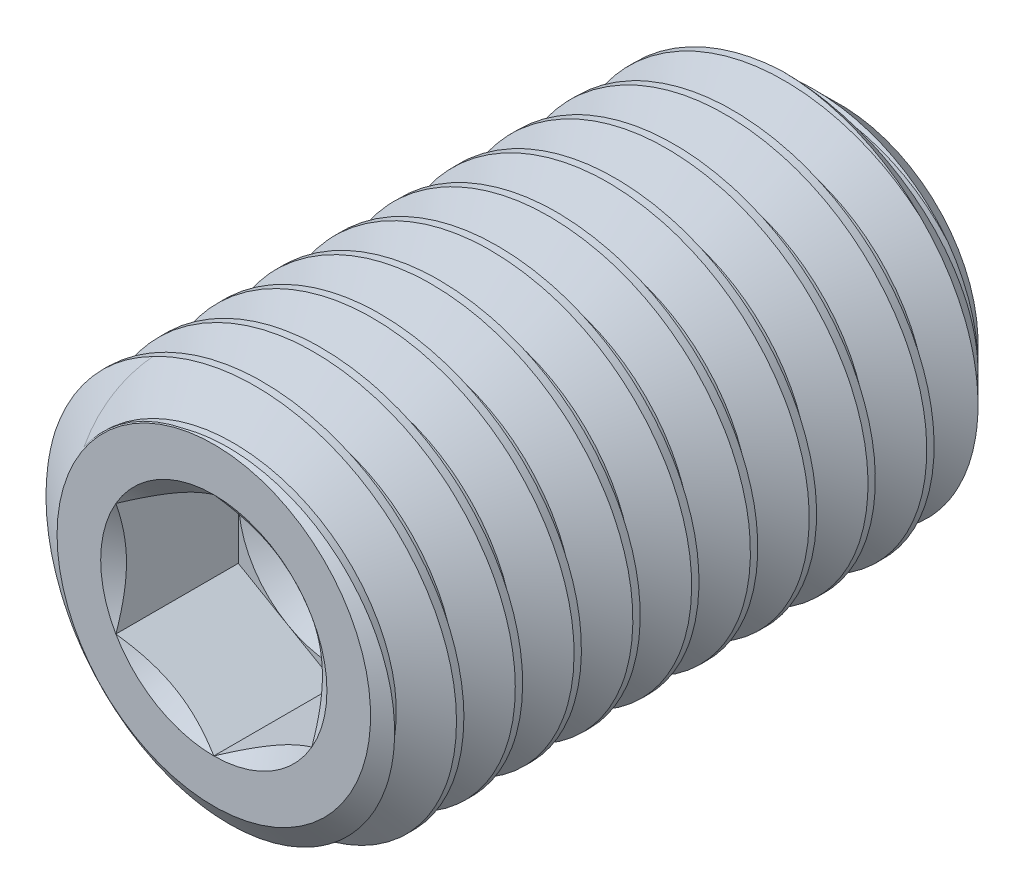
SolidWorks part; units mm, degrees
ref_plane "Front" through (0, 0, 0) normal (0, 0, 1) x (1, 0, 0)
ref_plane "Top" through (0, 0, 0) normal (0, 1, 0) x (1, 0, 0)
ref_plane "Right" through (0, 0, 0) normal (1, 0, 0) x (0, 0, -1)
sketch "Sketch22" plane through (0, 0, 0) normal (1, 0, 0) x (0, 0, -1)
  line L0 (-8, 0) -> (-8, 4)
  line L1 (-8, 4) -> (-7.2998, 5)
  line L2 (-7.2998, 5) -> (6.5, 5)
  line L3 (6.5, 5) -> (8, 3.5)
  line L4 (-0.3999, 5) -> (-0.3999, -5) construction
  line L5 (8, 0) -> (-8, 0)
  line L6 (-8, 4) -> (-8, -4) construction
  line L7 (8, 0) -> (8, 3.5)
  point P11 (-0.3999, 0)
  dimension "Length" = 16
  dimension "D3" = 35
  dimension "D6" = 45
  dimension "Dia" = 10
  dimension "D1" = 8
  dimension "D2" = 1.5
revolve "Revolve1" add sketch "Sketch22" angle 360 about L5
ref_plane "Plane1" through (0, 0, -8) normal (0, 0, 1) x (1, 0, 0)
sketch "Sketch27" plane through (0, 0, -8) normal (0, 0, 1) x (1, 0, 0)
  circle A0 centre (0, 0) radius 5 construction
  circle A1 centre (0, 0) radius 5
curve "Helix/Spiral1" pitch 1.5 height 17.5 radius 5 centre (0, 0, -8) axis (0, 0, 1) start towards (0, 1, 0)
sketch "Sketch28" plane through (0, 0, 0) normal (1, 0, 0) x (0, 0, -1)
  line L0 (8, 5) -> (9.3125, 5)
  line L1 (9.3125, 5) -> (8.75, 4.0257)
  line L2 (8.75, 4.0257) -> (8.5625, 4.0257)
  line L3 (8.5625, 4.0257) -> (8, 5)
  line L4 (8.2812, 4.5129) -> (9.0313, 4.5129) construction
  line L6 (-7.2998, 5) -> (6.5, 5) construction
  dimension "D1" = 0.1875
  dimension "D3" = 60
  dimension "D2" = 0.75
sweep "Cut-Sweep2" cut profiles "Sketch28" path "Helix/Spiral1" align with end faces yes
sketch "Sketch23" plane through (0, 0, 8) normal (0, 0, 1) x (1, 0, 0)
  line L1 (0, 2.8868) -> (-2.5, 1.4434)
  line L2 (-2.5, 1.4434) -> (-2.5, -1.4434)
  line L3 (-2.5, -1.4434) -> (0, -2.8868)
  line L4 (0, -2.8868) -> (2.5, -1.4434)
  line L5 (2.5, -1.4434) -> (2.5, 1.4434)
  line L6 (2.5, 1.4434) -> (0, 2.8868)
  circle A0 centre (0, 0) radius 2.5 construction
  dimension "Hex" = 5
extrude "Cut-Extrude10" cut sketch "Sketch23" against normal blind 3.125
sketch "Sketch24" plane through (0, 0, 8) normal (0, 0, 1) x (1, 0, 0)
  circle A0 centre (0, 0) radius 2.8868
extrude "Cut-Extrude11" cut sketch "Sketch24" against normal through all draft 55
sketch "Sketch26" plane through (0, 0, 4.875) normal (0, 0, 1) x (1, 0, 0)
  circle A0 centre (0, 0) radius 2.5 construction
  circle A1 centre (0, 0) radius 2.5
extrude "Cut-Extrude12" cut sketch "Sketch26" against normal through all draft 60
sketch "Sketch30" plane through (0, 0, 0) normal (1, 0, 0) x (0, 0, -1)
  line L0 (-7.2998, 5) -> (6.5, 5) construction
  line L1 (-8, 0) -> (-8, 4) construction
  line L2 (8, 0) -> (8, 3.5) construction
  point P0 (-8, 5)
  point P1 (8, 5)
  point P2 (8, -5)
  point P11 (4.25, -5)
  dimension "D1" = 3.75
equation "\"D1@Sketch28\" = \"D4@Helix/Spiral1\" * .125"
equation "\"D2@Sketch28\" = \"D4@Helix/Spiral1\" * .5"
equation "\"D3@Helix/Spiral1\" = \"Length@Sketch22\" + \"D4@Helix/Spiral1\""
equation "\"D1@Sketch30\" = \"D4@Helix/Spiral1\" * 2.5"
equation "\"hex Depth@Cut-Extrude10\" = \"Hex@Sketch23\" * .625"
equation "\"D1@Sketch22\" = \"Dia@Sketch22\" * .8"
equation "\"D2@Sketch22\" = \"D4@Helix/Spiral1\""
